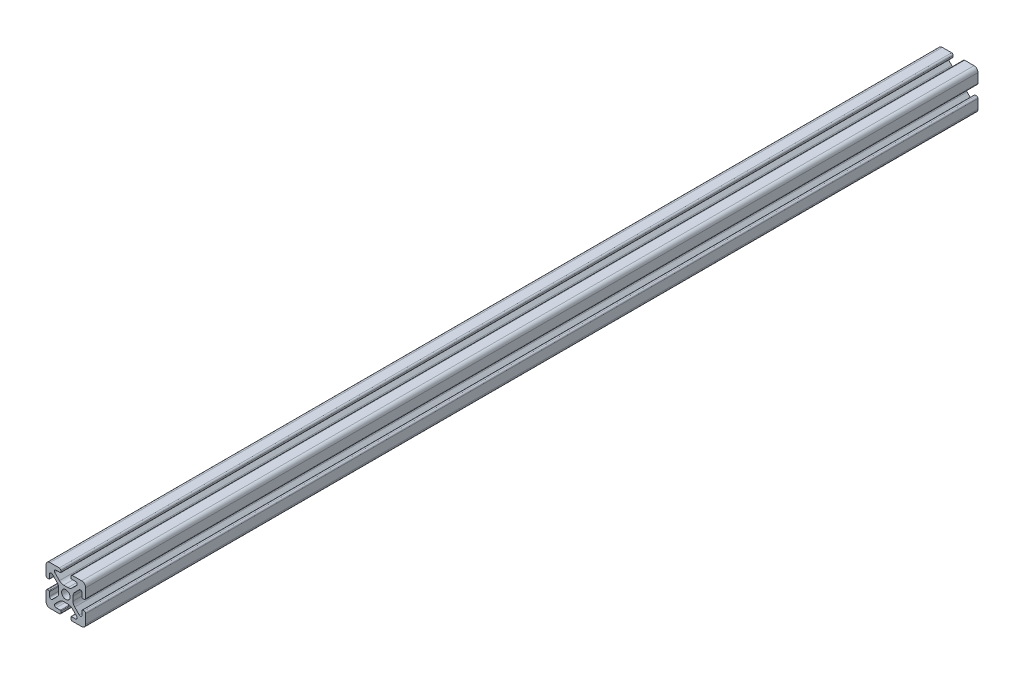
SolidWorks part; units mm, degrees
ref_plane "Front Plane" through (0, 0, 0) normal (0, 0, 1) x (1, 0, 0)
ref_plane "Top Plane" through (0, 0, 0) normal (0, 1, 0) x (1, 0, 0)
ref_plane "Right Plane" through (0, 0, 0) normal (1, 0, 0) x (0, 0, -1)
sketch "Sketch1" plane through (0, 0, 0) normal (0, 0, 1) x (1, 0, 0)
  line L0 (0, 10) -> (0, -10) construction
  line L1 (10, 0) -> (-10, 0) construction
  line L2 (-2.5, 10) -> (2.5, 10) construction
  line L3 (-5.75, 8.2) -> (5.75, 8.2) construction
  circle A0 centre (0, 0) radius 2.15 construction
  point P4 (0, 0)
  point P8 (0, 0)
  point P10 (0, 3.6)
  point P14 (0, 10)
  point P17 (0, 8.2)
  dimension "Thru Hole" = 4.3
  dimension "Height" = 20
  dimension "T Slot Depth" = 6.4
  dimension "T Slot Top Width" = 5
  dimension "T Slot Max Width" = 11.5
  dimension "Wall" = 1.8
sketch "Sketch2" plane through (0, 0, 0) normal (1, 0, 0) x (0, 0, -1)
  line L0 (225, 0) -> (-225, 0) construction
  point P4 (0, 0)
  dimension "D1" = 450
sketch "Sketch3" plane through (0, 0, 0) normal (0, 0, 1) x (1, 0, 0)
  line L0 (3.2874, 10) -> (8, 10)
  line L1 (10, 8) -> (10, -8) construction
  line L2 (8, -10) -> (-8, -10) construction
  line L3 (-10, 10) -> (10, -10) construction
  line L4 (2.5, 9.2126) -> (2.5, 8.5048)
  line L5 (-5.75, 8.2) -> (5.75, 8.2) construction
  line L6 (2.8048, 8.2) -> (4.9118, 8.2)
  line L7 (5.5045, 6.7691) -> (3.2141, 4.4787)
  line L8 (1.0928, 3.6) -> (-1.0928, 3.6)
  line L9 (0, 10) -> (0, -10) construction
  line L10 (5.75, 8.2) -> (5.75, 0) construction
  line L11 (10, 0) -> (-10, 0) construction
  line L12 (0, 0) -> (0, 10) construction
  line L13 (-2.5, 9.2126) -> (-2.5, 8.5048)
  line L14 (-5.5045, 6.7691) -> (-3.2141, 4.4787)
  line L15 (-2.8048, 8.2) -> (-4.9118, 8.2)
  line L16 (-3.2874, 10) -> (-8, 10)
  line L17 (0, 0) -> (-10, 0) construction
  line L18 (-10, 3.2874) -> (-10, 8)
  line L19 (-8.2, 2.8048) -> (-8.2, 4.9118)
  line L20 (-6.7691, 5.5045) -> (-4.4787, 3.2141)
  line L21 (-9.2126, 2.5) -> (-8.5048, 2.5)
  line L22 (-3.6, -1.0928) -> (-3.6, 1.0928)
  line L23 (-6.7691, -5.5045) -> (-4.4787, -3.2141)
  line L24 (-8.2, -2.8048) -> (-8.2, -4.9118)
  line L25 (-9.2126, -2.5) -> (-8.5048, -2.5)
  line L26 (-10, -3.2874) -> (-10, -8)
  line L27 (9.2126, -2.5) -> (8.5048, -2.5)
  line L28 (8.2, -2.8048) -> (8.2, -4.9118)
  line L29 (6.7691, -5.5045) -> (4.4787, -3.2141)
  line L30 (3.6, -1.0928) -> (3.6, 1.0928)
  line L31 (9.2126, 2.5) -> (8.5048, 2.5)
  line L32 (6.7691, 5.5045) -> (4.4787, 3.2141)
  line L33 (8.2, 2.8048) -> (8.2, 4.9118)
  line L34 (10, 8) -> (10, 3.2874)
  line L35 (10, -3.2874) -> (10, -8)
  line L36 (3.2874, -10) -> (8, -10)
  line L37 (-3.2874, -10) -> (-8, -10)
  line L38 (-6.7691, -5.5045) -> (-4.4787, -3.2141)
  line L39 (-2.8048, -8.2) -> (-4.9118, -8.2)
  line L40 (-5.5045, -6.7691) -> (-3.2141, -4.4787)
  line L41 (-2.5, -9.2126) -> (-2.5, -8.5048)
  line L42 (1.0928, -3.6) -> (-1.0928, -3.6)
  line L43 (5.5045, -6.7691) -> (3.2141, -4.4787)
  line L44 (2.8048, -8.2) -> (4.9118, -8.2)
  line L45 (2.5, -9.2126) -> (2.5, -8.5048)
  arc A0 (4.9118, 8.2) -> (5.5045, 6.7691) centre (4.9118, 7.3618) cw
  arc A1 (3.2141, 4.4787) -> (1.0928, 3.6) centre (1.0928, 6.6) cw
  circle A2 centre (0, 0) radius 2.15 construction
  circle A3 centre (0, 0) radius 2.15
  arc A4 (3.2874, 10) -> (2.5, 9.2126) centre (3.2874, 9.2126) ccw
  arc A5 (2.5, 8.5048) -> (2.8048, 8.2) centre (2.8048, 8.5048) ccw
  arc A6 (-3.2874, 10) -> (-2.5, 9.2126) centre (-3.2874, 9.2126) cw
  arc A7 (-4.9118, 8.2) -> (-5.5045, 6.7691) centre (-4.9118, 7.3618) ccw
  arc A8 (-3.2141, 4.4787) -> (-1.0928, 3.6) centre (-1.0928, 6.6) ccw
  arc A9 (-2.5, 8.5048) -> (-2.8048, 8.2) centre (-2.8048, 8.5048) cw
  arc A10 (-8.5048, 2.5) -> (-8.2, 2.8048) centre (-8.5048, 2.8048) ccw
  arc A11 (-4.4787, 3.2141) -> (-3.6, 1.0928) centre (-6.6, 1.0928) cw
  arc A12 (-8.2, 4.9118) -> (-6.7691, 5.5045) centre (-7.3618, 4.9118) cw
  arc A13 (-10, 3.2874) -> (-9.2126, 2.5) centre (-9.2126, 3.2874) ccw
  arc A14 (-8.5048, -2.5) -> (-8.2, -2.8048) centre (-8.5048, -2.8048) cw
  arc A15 (-10, -3.2874) -> (-9.2126, -2.5) centre (-9.2126, -3.2874) cw
  arc A16 (-4.4787, -3.2141) -> (-3.6, -1.0928) centre (-6.6, -1.0928) ccw
  arc A17 (-8.2, -4.9118) -> (-6.7691, -5.5045) centre (-7.3618, -4.9118) ccw
  arc A26 (-8, -10) -> (-10, -8) centre (-8, -8) cw
  arc A27 (-8, 10) -> (-10, 8) centre (-8, 8) ccw
  arc A28 (8, 10) -> (10, 8) centre (8, 8) cw
  arc A29 (10, -8) -> (8, -10) centre (8, -8) cw
  arc A30 (8.2, -4.9118) -> (6.7691, -5.5045) centre (7.3618, -4.9118) cw
  arc A31 (4.4787, -3.2141) -> (3.6, -1.0928) centre (6.6, -1.0928) cw
  arc A32 (10, -3.2874) -> (9.2126, -2.5) centre (9.2126, -3.2874) ccw
  arc A33 (8.5048, -2.5) -> (8.2, -2.8048) centre (8.5048, -2.8048) ccw
  arc A34 (10, 3.2874) -> (9.2126, 2.5) centre (9.2126, 3.2874) cw
  arc A35 (8.2, 4.9118) -> (6.7691, 5.5045) centre (7.3618, 4.9118) ccw
  arc A36 (4.4787, 3.2141) -> (3.6, 1.0928) centre (6.6, 1.0928) ccw
  arc A37 (8.5048, 2.5) -> (8.2, 2.8048) centre (8.5048, 2.8048) cw
  arc A38 (-2.5, -8.5048) -> (-2.8048, -8.2) centre (-2.8048, -8.5048) ccw
  arc A39 (-3.2141, -4.4787) -> (-1.0928, -3.6) centre (-1.0928, -6.6) cw
  arc A40 (-4.9118, -8.2) -> (-5.5045, -6.7691) centre (-4.9118, -7.3618) cw
  arc A41 (-3.2874, -10) -> (-2.5, -9.2126) centre (-3.2874, -9.2126) ccw
  arc A42 (2.5, -8.5048) -> (2.8048, -8.2) centre (2.8048, -8.5048) cw
  arc A43 (3.2874, -10) -> (2.5, -9.2126) centre (3.2874, -9.2126) cw
  arc A44 (3.2141, -4.4787) -> (1.0928, -3.6) centre (1.0928, -6.6) ccw
  arc A45 (4.9118, -8.2) -> (5.5045, -6.7691) centre (4.9118, -7.3618) ccw
  point P36 (2.5, 10)
  point P39 (2.5, 8.2)
  point P49 (0, 3.6)
  point P77 (-3.6, 0)
  point P78 (-8.2, -2.5)
  point P79 (-10, -2.5)
  point P104 (-10, -10)
  point P110 (10, 10)
  point P114 (10, -2.5)
  point P115 (8.2, -2.5)
  point P116 (3.6, 0)
  point P141 (0, -3.6)
  dimension "D1" = 3
  dimension "D2" = 0.8382
  dimension "D4" = 0.7874
  dimension "D5" = 0.3048
  dimension "D6" = 2
  dimension "D3" = 45
extrude "Boss-Extrude1" add sketch "Sketch3" along normal up to vertex (225 mm away) and the other way up to vertex (225 mm away) contours A45 L44 A42 L45 A43 L36 A29 L35 A32 L27 A33 L28 A30 L29 A31 L30 A36 L32 A35 L33 A37 L31 A34 L34 A28 L0 A4 L4 A5 L6 A0 L7 A1 L8 A8 L14 A7 L15 A9 L13 A6 L16 A27 L18 A13 L21 A10 L19 A12 L20 A11 region at (5.6437, 9.7172, 0) up to point (0, 0, 225) other way up to point (0, 0, -225)
